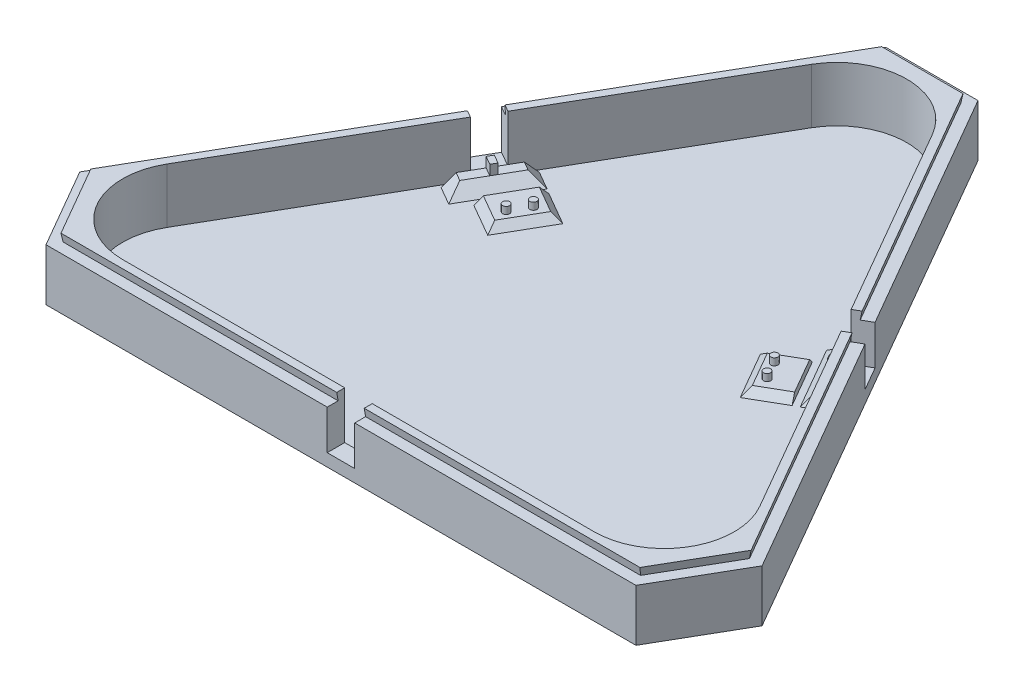
SolidWorks part; units mm, degrees
ref_plane "Plan de face" through (0, 0, 0) normal (0, 0, 1) x (1, 0, 0)
ref_plane "Plan de dessus" through (0, 0, 0) normal (0, 1, 0) x (1, 0, 0)
ref_plane "Plan de droite" through (0, 0, 0) normal (1, 0, 0) x (0, 0, -1)
sketch "Esquisse1" plane through (0, 0, 0) normal (0, 1, 0) x (1, 0, 0)
  line L3 (-77.5, -44.7446) -> (77.5, -44.7446)
  line L4 (77.5, -44.7446) -> (0, 89.4893)
  line L5 (0, 89.4893) -> (-77.5, -44.7446)
  line L6 (0, 89.4893) -> (0, -44.7446) construction
  line L7 (77.5, -44.7446) -> (-38.75, 22.3723) construction
  dimension "D1" = 155
extrude "Boss.-Extru.1" add sketch "Esquisse1" along normal blind 12 separate body
ref_axis "Axe1" through (0, -0.9, 0) along (0, 1, 0)
sketch "Esquisse2" plane through (0, 12, 0) normal (0, 1, 0) x (1, 0, 0)
  line L0 (-9.2376, 73.4893) -> (9.2376, 73.4893)
  line L1 (0, 89.4893) -> (-77.5, -44.7446) construction
  line L2 (77.5, -44.7446) -> (0, 89.4893) construction
  line L3 (9.2376, 73.4893) -> (0, 89.4893)
  line L4 (0, 89.4893) -> (-9.2376, 73.4893)
  line L5 (77.5, -44.7446) -> (68.2624, -28.7446)
  line L6 (68.2624, -28.7446) -> (59.0248, -44.7446)
  line L7 (59.0248, -44.7446) -> (77.5, -44.7446)
  line L8 (-77.5, -44.7446) -> (-59.0248, -44.7446)
  line L9 (-59.0248, -44.7446) -> (-68.2624, -28.7446)
  line L10 (-68.2624, -28.7446) -> (-77.5, -44.7446)
  point P6 (0, 73.4893)
  point P17 (0, 0)
  dimension "D1" = 16
extrude "Enlèv. mat.-Extru.1" cut sketch "Esquisse2" against normal through all
sketch "Esquisse10" plane through (0, 12, 0) normal (0, 1, 0) x (1, 0, 0)
  line L0 (-9.2376, 73.4893) -> (9.2376, 73.4893) construction
  circle A0 centre (0, 70.9893) radius 1.65
  circle A1 centre (61.4785, -35.4946) radius 1.65
  circle A2 centre (-61.4785, -35.4946) radius 1.65
  point P9 (0, 0)
  dimension "D1" = 3.3
  dimension "D2" = 2.5
  dimension "D3" = 3
extrude "Enlèv. mat.-Extru.6" [suppressed] cut sketch "Esquisse10" against normal through all
sketch "Esquisse3" plane through (0, 12, 0) normal (0, 1, 0) x (1, 0, 0)
  line L3 (12.1244, 61.4893) -> (-12.1244, 61.4893) construction
  line L4 (59.3135, -20.2446) -> (12.1244, 61.4893)
  line L5 (-12.1244, 61.4893) -> (-59.3135, -20.2446)
  line L10 (-9.2376, 73.4893) -> (9.2376, 73.4893) construction
  line L11 (-47.1891, -41.2446) -> (47.1891, -41.2446)
  line L12 (59.0132, -34.7407) -> (-47.6968, 28.0788) construction
  line L13 (0, -41.6074) -> (0, 68.4893) construction
  line L14 (47.9131, 27.5989) -> (-59.0132, -34.7407) construction
  line L15 (-9.2376, 73.4893) -> (-68.2624, -28.7446) construction
  line L16 (68.2624, -28.7446) -> (9.2376, 73.4893) construction
  line L17 (-59.0248, -44.7446) -> (59.0248, -44.7446) construction
  arc A3 (12.1244, 61.4893) -> (-12.1244, 61.4893) centre (0, 54.4893) ccw
  arc A4 (47.1891, -41.2446) -> (59.3135, -20.2446) centre (47.1891, -27.2446) ccw
  arc A5 (-59.3135, -20.2446) -> (-47.1891, -41.2446) centre (-47.1891, -27.2446) ccw
  point P23 (0, 0)
  dimension "D2" = 14
  dimension "D1" = 3.5
  dimension "D4" = 3.5
  dimension "D5" = 3.5
  dimension "D3" = 3
extrude "Enlèv. mat.-Extru.2" cut sketch "Esquisse3" against normal blind 11
sketch "Esquisse4" plane through (0, 12, 0) normal (0, 1, 0) x (1, 0, 0)
  line L0 (37.0939, 18.2408) -> (34.3439, 23.0039)
  line L1 (59.3135, -20.2446) -> (12.1244, 61.4893) construction
  line L2 (34.3439, 23.0039) -> (37.375, 24.7539)
  line L3 (68.2624, -28.7446) -> (9.2376, 73.4893) construction
  line L4 (37.375, 24.7539) -> (40.125, 19.9908)
  line L5 (40.125, 19.9908) -> (37.0939, 18.2408)
  line L14 (-2.75, -44.7446) -> (-2.75, -41.2446)
  line L15 (-2.75, -41.2446) -> (2.75, -41.2446)
  line L16 (2.75, -41.2446) -> (2.75, -44.7446)
  line L17 (2.75, -44.7446) -> (-2.75, -44.7446)
  line L18 (-37.375, 24.7539) -> (-34.3439, 23.0039)
  line L19 (-34.3439, 23.0039) -> (-37.0939, 18.2408)
  line L20 (-37.0939, 18.2408) -> (-40.125, 19.9908)
  line L21 (-40.125, 19.9908) -> (-37.375, 24.7539)
  point P9 (38.75, 22.3723)
  point P10 (38.75, 22.3723)
  point P21 (0, 0)
  dimension "D1" = 5.5
  dimension "D2" = 3
extrude "Enlèv. mat.-Extru.3" cut sketch "Esquisse4" against normal blind 9.5
sketch "Esquisse5" plane through (0, 1, 0) normal (0, 1, 0) x (1, 0, 0)
  line L0 (27.3541, 18.9106) -> (30.0541, 14.2341)
  line L2 (28.8221, 12.368) -> (25.1221, 18.7766)
  line L4 (40.125, 19.9908) -> (37.375, 24.7539) construction
  line L5 (59.3135, -20.2446) -> (12.1244, 61.4893) construction
  line L6 (28.7041, 16.5723) -> (38.75, 22.3723) construction
  line L7 (27.3541, 18.9106) -> (29.9522, 20.4106)
  line L8 (29.9522, 20.4106) -> (29.4522, 21.2766)
  line L9 (29.4522, 21.2766) -> (25.1221, 18.7766)
  line L11 (33.1522, 14.868) -> (28.8221, 12.368)
  line L12 (32.6522, 15.7341) -> (33.1522, 14.868)
  line L13 (30.0541, 14.2341) -> (32.6522, 15.7341)
  dimension "D1" = 8.1
  dimension "D2" = 1
  dimension "D3" = 2.7
  dimension "D4" = 2
  dimension "D5" = 5
ref_plane "Plan2" through (0, 0, 0) normal (-1, 0, 0) x (0, 0, 1)
ref_plane "Plan3" through (0, 0, 0) normal (-0.5, 0, 0.866) x (0.866, 0, 0.5)
ref_plane "Plan4" through (0, 0, 0) normal (0.5, 0, 0.866) x (0.866, 0, -0.5)
sketch "Esquisse11" plane through (0, 0, 41.2446) normal (0, 0, -1) x (-1, 0, 0)
  line L0 (47.1891, 1) -> (-47.1891, 1) construction
  line L2 (-47.1891, 1) -> (-47.1891, 12) construction
  line L3 (0, 0) -> (0, 20.2129) construction
  circle A0 centre (-32.1891, 6.5) radius 5.15
  circle A1 centre (32.1891, 6.5) radius 5.15
  dimension "D1" = 10.3
  dimension "D3" = 15
  dimension "D2" = 5.5
extrude "Enlèv. mat.-Extru.7" [suppressed] cut sketch "Esquisse11" against normal blind 2
pattern_circular "Répétition circulaire1" [suppressed] count 3 over 360 about axis through (0, -0.9, 0) along (0, 1, 0) of bodies 123
chamfer "Chanfrein1" [suppressed] distance 0.4 angle 45
ref_plane "Plan5" through (0, 6.5, 0) normal (0, 1, 0) x (1, 0, 0)
sketch "Esquisse12" plane through (0, 1, 0) normal (0, 1, 0) x (1, 0, 0)
  line L0 (23.9284, 16.6441) -> (28.0284, 9.5427)
  line L1 (23.9284, 16.6441) -> (29.2978, 19.7441)
  line L2 (28.0284, 9.5427) -> (33.3978, 12.6427)
  line L3 (29.2978, 19.7441) -> (33.3978, 12.6427)
  line L4 (59.3135, -20.2446) -> (12.1244, 61.4893) construction
  line L6 (37.0939, 18.2408) -> (40.125, 19.9908) construction
  dimension "D1" = 8.2
  dimension "D2" = 6.2
  dimension "D3" = 6
  dimension "D4" = 3
extrude "Boss.-Extru.2" add sketch "Esquisse12" along normal blind 1.4
sketch "Esquisse13" plane through (0, 2.4, 0) normal (0, 1, 0) x (1, 0, 0)
  line L0 (26.364, 15.6254) -> (28.364, 12.1613) construction
  line L1 (33.3978, 12.6427) -> (29.2978, 19.7441) construction
  line L2 (27.364, 13.8934) -> (31.3478, 16.1934) construction
  line L3 (23.9284, 16.6441) -> (28.0284, 9.5427) construction
  circle A0 centre (26.364, 15.6254) radius 0.7
  circle A1 centre (28.364, 12.1613) radius 0.7
  dimension "D1" = 1.4
  dimension "D2" = 4
  dimension "D3" = 1.6
extrude "Boss.-Extru.3" add sketch "Esquisse13" along normal blind 1.4
sketch "Esquisse14" plane through (0, 1, 0) normal (0, 1, 0) x (1, 0, 0)
  line L4 (34.3439, 23.0039) -> (37.0939, 18.2408) construction
  line L5 (35.7189, 20.6223) -> (35.1993, 20.3223) construction
  line L6 (59.3135, -20.2446) -> (12.1244, 61.4893) construction
  line L7 (32.6993, 24.6524) -> (37.6993, 15.9922)
  line L8 (32.6993, 24.6524) -> (30.9672, 23.6524)
  line L9 (37.6993, 15.9922) -> (35.9672, 14.9922)
  line L10 (30.9672, 23.6524) -> (35.9672, 14.9922)
  line L11 (59.3135, -20.2446) -> (12.1244, 61.4893) construction
  dimension "D1" = 10
  dimension "D2" = 2
  dimension "D3" = 0.6
extrude "Boss.-Extru.6" add sketch "Esquisse14" along normal blind 2.2
sketch "Esquisse15" plane through (0, 3.2, 0) normal (0, 1, 0) x (1, 0, 0)
  line L0 (34.8993, 20.8419) -> (35.4993, 19.8027)
  line L1 (34.8993, 20.8419) -> (33.1672, 19.8419)
  line L2 (35.4993, 19.8027) -> (33.7672, 18.8027)
  line L3 (33.1672, 19.8419) -> (33.7672, 18.8027)
  line L4 (37.6993, 15.9922) -> (32.6993, 24.6524) construction
  line L5 (30.9672, 23.6524) -> (35.9672, 14.9922) construction
  line L6 (37.6993, 15.9922) -> (32.6993, 24.6524) construction
  point P11 (35.1993, 20.3223)
  point P12 (35.1993, 20.3223)
  dimension "D1" = 1.2
extrude "Boss.-Extru.7" add sketch "Esquisse15" along normal blind 2
chamfer "Chanfrein3" distance 2.2 angle 45 3 edges at (33.4672, 1, -19.3223) (36.8333, 1, -15.4922) (31.8333, 1, -24.1524)
chamfer "Chanfrein4" distance 1.4 angle 45 3 edges at (26.6131, 1, -18.1941) (25.9784, 1, -13.0934) (30.7131, 1, -11.0927)
pattern_circular "Répétition circulaire2" count 2 over 120 about axis through (0, -0.9, 0) along (0, 1, 0) of "Boss.-Extru.2", "Boss.-Extru.3", "Boss.-Extru.6", "Boss.-Extru.7", "Chanfrein3", "Chanfrein4"
sketch "Esquisse16" plane through (0, 0, 0) normal (0, 1, 0) x (1, 0, 0)
  line L0 (11.2217, 27.4997) -> (41.3465, -26.6864)
  line L1 (-19.3685, 82.5231) -> (-119.2403, 26.9993)
  line L2 (72.2349, -82.2461) -> (-27.6369, -137.7698)
  line L3 (-119.2403, 26.9993) -> (-27.6369, -137.7698)
  line L4 (-19.3685, 82.5231) -> (51.5403, 121.9449)
  line L6 (51.5403, 121.9449) -> (82.1306, 66.9215)
  line L7 (11.2217, 27.4997) -> (82.1306, 66.9215)
  line L8 (72.2349, -82.2461) -> (117.9546, -56.8282)
  line L10 (117.9546, -56.8282) -> (87.0662, -1.2686)
  line L11 (41.3465, -26.6864) -> (87.0662, -1.2686)
extrude "Enlèv. mat.-Extru.9" [suppressed] cut sketch "Esquisse16" along normal through all
sketch "Esquisse17" plane through (0, 12, 0) normal (0, 1, 0) x (1, 0, 0)
  line L0 (37.375, 24.7539) -> (9.2376, 73.4893) construction
  line L1 (-9.2376, 73.4893) -> (9.2376, 73.4893) construction
  line L2 (-9.2376, 73.4893) -> (-37.375, 24.7539) construction
  line L3 (-40.125, 19.9908) -> (-68.2624, -28.7446) construction
  line L4 (-59.0248, -44.7446) -> (-68.2624, -28.7446) construction
  line L5 (-59.0248, -44.7446) -> (-2.75, -44.7446) construction
  line L6 (2.75, -44.7446) -> (59.0248, -44.7446) construction
  line L7 (68.2624, -28.7446) -> (59.0248, -44.7446) construction
  line L8 (68.2624, -28.7446) -> (40.125, 19.9908) construction
  line L9 (37.375, 24.7539) -> (9.2376, 73.4893)
  line L10 (-9.2376, 73.4893) -> (9.2376, 73.4893)
  line L11 (-9.2376, 73.4893) -> (-37.375, 24.7539)
  line L12 (-40.125, 19.9908) -> (-68.2624, -28.7446)
  line L13 (-59.0248, -44.7446) -> (-68.2624, -28.7446)
  line L14 (-59.0248, -44.7446) -> (-2.75, -44.7446)
  line L15 (2.75, -44.7446) -> (59.0248, -44.7446)
  line L16 (68.2624, -28.7446) -> (59.0248, -44.7446)
  line L17 (68.2624, -28.7446) -> (40.125, 19.9908)
extrude "Enlèv. de mat.-Extru.-Mince1" cut sketch "Esquisse17" against normal blind 1.6 draft 10 thin draft outward yes thin type one direction reverse wall 1.9
equation "\"D5@Esquisse3\"=\"D1@Esquisse3\""
equation "\"D4@Esquisse3\"=\"D1@Esquisse3\""
